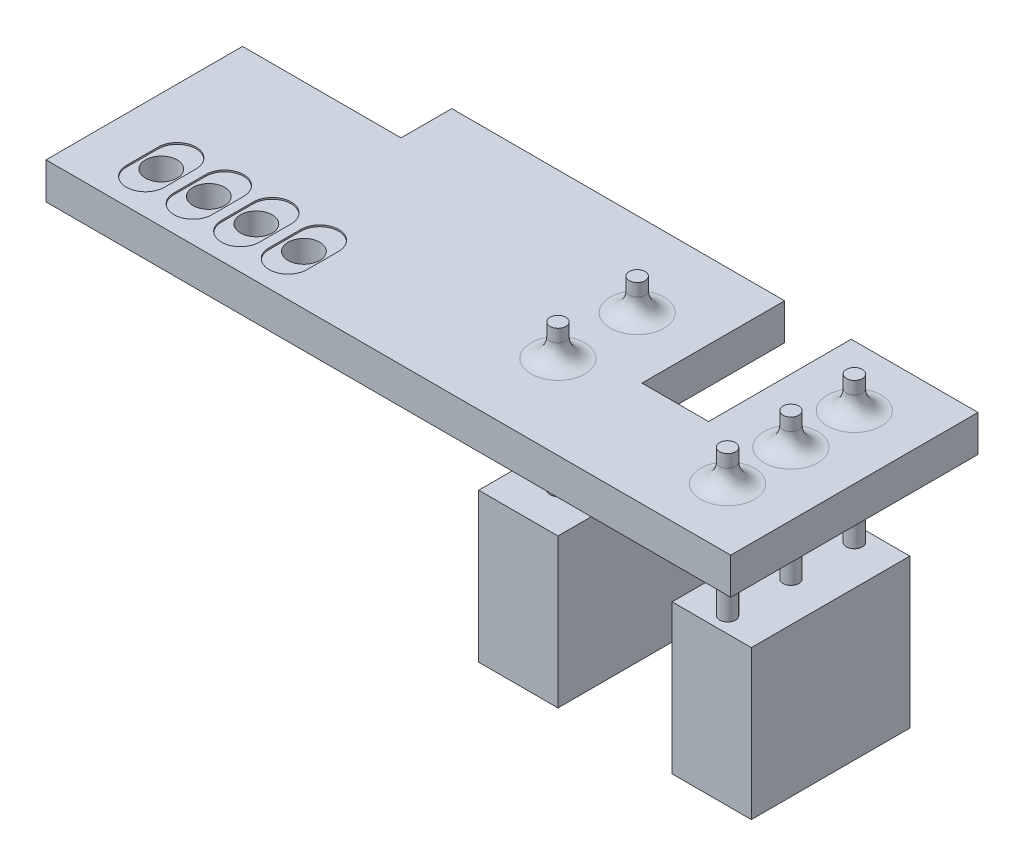
SolidWorks part; units mm, degrees
ref_plane "Front Plane" through (0, 0, 0) normal (0, 0, 1) x (1, 0, 0)
ref_plane "Top Plane" through (0, 0, 0) normal (0, 1, 0) x (1, 0, 0)
ref_plane "Right Plane" through (0, 0, 0) normal (1, 0, 0) x (0, 0, -1)
sketch "Sketch1" plane through (0, 0, 0) normal (0, 1, 0) x (1, 0, 0)
  line L0 (-16.6, 0) -> (-16.6, -1.6)
  line L1 (-16.6, 0) -> (-6.1, 0)
  line L2 (-6.1, 0) -> (-6.1, -4.5)
  line L3 (-6.1, -4.5) -> (-4, -4.5)
  line L4 (-4, -4.5) -> (-4, 0)
  line L5 (-4, 0) -> (0, 0)
  line L6 (0, 0) -> (0, -7.8)
  line L7 (0, -7.8) -> (-21.6, -7.8)
  line L8 (-15.082, -6.1822) -> (-16.582, -6.1822) construction
  line L9 (-16.582, -6.1822) -> (-18.082, -6.1822) construction
  line L10 (-18.082, -6.1822) -> (-19.582, -6.1822) construction
  line L11 (-16.6, -1.6) -> (-21.6, -1.6)
  line L12 (-21.6, -1.6) -> (-21.6, -7.8)
  circle A0 centre (-19.582, -6.1822) radius 0.5
  circle A1 centre (-18.082, -6.1822) radius 0.5
  circle A2 centre (-16.582, -6.1822) radius 0.5
  circle A3 centre (-15.082, -6.1822) radius 0.5
  dimension "D8" = 1
  dimension "D1" = 1.6
  dimension "D2" = 7.8
  dimension "D3" = 2.1
  dimension "D4" = 4.5
  dimension "D5" = 10.5
  dimension "D6" = 4
  dimension "D7" = 4.5
  dimension "D9" = 5
extrude "Boss-Extrude1" add sketch "Sketch1" along normal blind 1.15
sketch "Sketch2" plane through (0, 1.15, 0) normal (0, 1, 0) x (1, 0, 0)
  line L0 (-8.1, -2.65) -> (-8.1, -5.15) construction
  line L1 (-8.1, -5.15) -> (-8.1, -3.9) construction
  line L2 (-8.1, -3.9) -> (-2, -3.9) construction
  line L3 (-2, -5.9) -> (-2, -1.9) construction
  line L4 (0, -7.8) -> (0, 0) construction
  line L5 (0, 0) -> (-4, 0) construction
  circle A0 centre (-8.1, -2.65) radius 0.25
  circle A1 centre (-8.1, -5.15) radius 0.25
  circle A2 centre (-2, -5.9) radius 0.25
  circle A3 centre (-2, -1.9) radius 0.25
  circle A4 centre (-2, -3.9) radius 0.25
  point P11 (0, -3.9)
  point P12 (-2, 0)
  point P13 (-2, -3.9)
  dimension "D1" = 0.5
  dimension "D2" = 4
  dimension "D3" = 2.5
  dimension "D4" = 6.1
extrude "Boss-Extrude2" add sketch "Sketch2" along normal blind 1 and the other way blind 3.6
sketch "Sketch3" plane through (0, -2.45, 0) normal (0, -1, 0) x (1, 0, 0)
  line L1 (-9.35, 6.4) -> (-6.85, 6.4)
  line L2 (-9.35, 6.4) -> (-9.35, 1.4)
  line L3 (-9.35, 1.4) -> (-6.85, 1.4)
  line L4 (-6.85, 6.4) -> (-6.85, 1.4)
  line L5 (-3.25, 6.4) -> (-0.75, 6.4)
  line L6 (-3.25, 6.4) -> (-3.25, 1.4)
  line L7 (-3.25, 1.4) -> (-0.75, 1.4)
  line L8 (-0.75, 6.4) -> (-0.75, 1.4)
  point P8 (-8.1, 5.15)
  point P9 (-8.1, 6.4)
  point P11 (-2, 5.9)
  point P12 (-2, 6.4)
  point P14 (-2, 3.9)
  point P15 (-0.75, 3.9)
  dimension "D1" = 5
  dimension "D2" = 2.5
extrude "Boss-Extrude3" add sketch "Sketch3" along normal blind 4.7
sketch "Sketch4" plane through (0, 1.15, 0) normal (0, 1, 0) x (1, 0, 0)
  line L0 (-15.082, -6.6822) -> (-15.082, -5.6822) construction
  line L1 (-15.6802, -6.6822) -> (-15.6802, -5.6822)
  line L2 (-14.4838, -6.6822) -> (-14.4838, -5.6822)
  line L3 (-16.582, -6.6822) -> (-16.582, -5.6822) construction
  line L4 (-17.1802, -6.6822) -> (-17.1802, -5.6822)
  line L5 (-15.9838, -6.6822) -> (-15.9838, -5.6822)
  line L6 (-18.082, -6.6822) -> (-18.082, -5.6822) construction
  line L7 (-18.6802, -6.6822) -> (-18.6802, -5.6822)
  line L8 (-17.4838, -6.6822) -> (-17.4838, -5.6822)
  line L9 (-19.582, -6.6822) -> (-19.582, -5.6822) construction
  line L10 (-20.1802, -6.6822) -> (-20.1802, -5.6822)
  line L11 (-18.9838, -6.6822) -> (-18.9838, -5.6822)
  arc A0 (-15.6802, -6.6822) -> (-14.4838, -6.6822) centre (-15.082, -6.6822) ccw
  arc A1 (-14.4838, -5.6822) -> (-15.6802, -5.6822) centre (-15.082, -5.6822) ccw
  arc A2 (-17.1802, -6.6822) -> (-15.9838, -6.6822) centre (-16.582, -6.6822) ccw
  arc A3 (-15.9838, -5.6822) -> (-17.1802, -5.6822) centre (-16.582, -5.6822) ccw
  arc A4 (-18.6802, -6.6822) -> (-17.4838, -6.6822) centre (-18.082, -6.6822) ccw
  arc A5 (-17.4838, -5.6822) -> (-18.6802, -5.6822) centre (-18.082, -5.6822) ccw
  arc A6 (-20.1802, -6.6822) -> (-18.9838, -6.6822) centre (-19.582, -6.6822) ccw
  arc A7 (-18.9838, -5.6822) -> (-20.1802, -5.6822) centre (-19.582, -5.6822) ccw
  circle A8 centre (-15.082, -6.1822) radius 0.5 construction
  point P2 (-15.082, -6.1822)
  point P9 (-16.582, -6.1822)
  point P17 (-18.082, -6.1822)
  point P25 (-19.582, -6.1822)
extrude "Cut-Extrude1" cut sketch "Sketch4" against normal blind 0.05
fillet "Fillet1" radius 0.6 5 edges at (-2, 1.15, 1.65) (-2, 1.15, 5.65) (-8.1, 1.15, 2.4) (-8.1, 1.15, 4.9) (-2, 1.15, 3.65)
sketch "Sketch5" plane through (0, 0, 0) normal (1, 0, 0) x (0, 0, -1)
  line L0 (-1.4, -7.15) -> (-1.4, -2.45) construction
  line L1 (-1.4, -2.45) -> (-6.4, -2.45) construction
  point P0 (0.6, -4.8)
  point P1 (-1.4, -4.8)
  point P2 (-3.9, -4.8)
  point P5 (-3.9, -2.45)
  point P8 (-8.4, -4.8)
  dimension "D1" = 4.5
  dimension "D2" = 4.5
ref_axis "Axis1" through (0, -4.8, -0.6) along (1, 0, 0)
ref_axis "new axis" through (0, -4.8, 8.4) along (-1, 0, 0)
ref_plane "Plane1" through (0, 0, 3.9) normal (0, 0, -1) x (-1, 0, 0)
ref_plane "Plane3" through (0, -4.8, 0) normal (0, 1, 0) x (1, 0, 0)
ref_plane "Plane2" through (0, -2.8, 0) normal (0, 1, 0) x (1, 0, 0)
